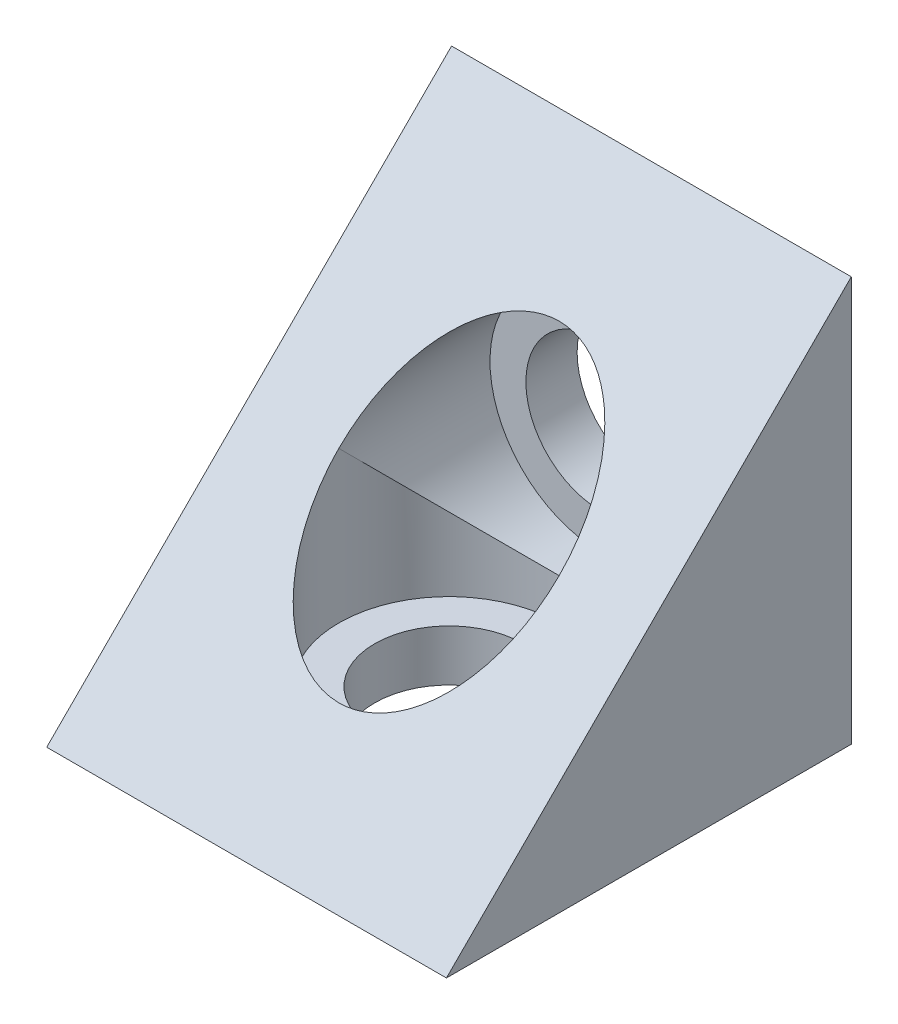
SolidWorks part; units mm, degrees
ref_plane "Front Plane" through (0, 0, 0) normal (0, 0, 1) x (1, 0, 0)
ref_plane "Top Plane" through (0, 0, 0) normal (0, 1, 0) x (1, 0, 0)
ref_plane "Right Plane" through (0, 0, 0) normal (1, 0, 0) x (0, 0, -1)
sketch "Sketch1" plane through (0, 0, 0) normal (1, 0, 0) x (0, 0, -1)
  line L0 (-10.033, -10.033) -> (10.033, 10.033)
  line L2 (10.033, 10.033) -> (10.033, -10.033)
  line L3 (10.033, -10.033) -> (-10.033, -10.033)
  line L5 (10.033, 10.033) -> (-10.033, -10.033) construction
  line L6 (10.033, -10.033) -> (0, 0) construction
  point P0 (0, 0)
  point P4 (8.769, -11.297)
  dimension "D1" = 20.066
  dimension "D2" = 20.066
extrude "Boss-Extrude1" add sketch "Sketch1" along normal mid plane 19.812
sketch "Sketch2" plane through (0, 0, 0) normal (0, 1, 0) x (1, 0, 0)
  circle A0 centre (0, 0) radius 5.461
  circle A1 centre (0, 0) radius 3.683
  dimension "D1" = 10.922
  dimension "D2" = 7.366
extrude "Cut-Extrude1" cut sketch "Sketch2" against normal offset from surface 2.54 and the other way through all contours A0 A1 | A1 region at (-5.3065, 0, 0) region at (0, 0, 0) up to face at (0, -10.033, 0)
extrude "Cut-Extrude2" cut sketch "Sketch2<3>" against normal through all contours A1 region at (0, 0, 0)
sketch "Sketch2<3>" plane through (0, 0, 0) normal (0, 1, 0) x (1, 0, 0) same geometry as "Sketch2"
sketch "Sketch3" plane through (0, 0, 0) normal (0, 0, 1) x (1, 0, 0)
  circle A0 centre (0, 0) radius 5.461
  circle A1 centre (0, 0) radius 5.461 construction
  circle A2 centre (0, 0) radius 3.683
  dimension "D1" = 7.366
extrude "Cut-Extrude3" cut sketch "Sketch3" against normal offset from surface (7.493 mm away) 2.54 contours A2 | A0 A2 region at (-5.3065, 0, 0) region at (0, 0, 0) up to face at (0, 0, -10.033)
extrude "Cut-Extrude4" cut sketch "Sketch3<4>" against normal through all contours A2 region at (0, 0, 0)
sketch "Sketch3<4>" plane through (0, 0, 0) normal (0, 0, 1) x (1, 0, 0) same geometry as "Sketch3"
